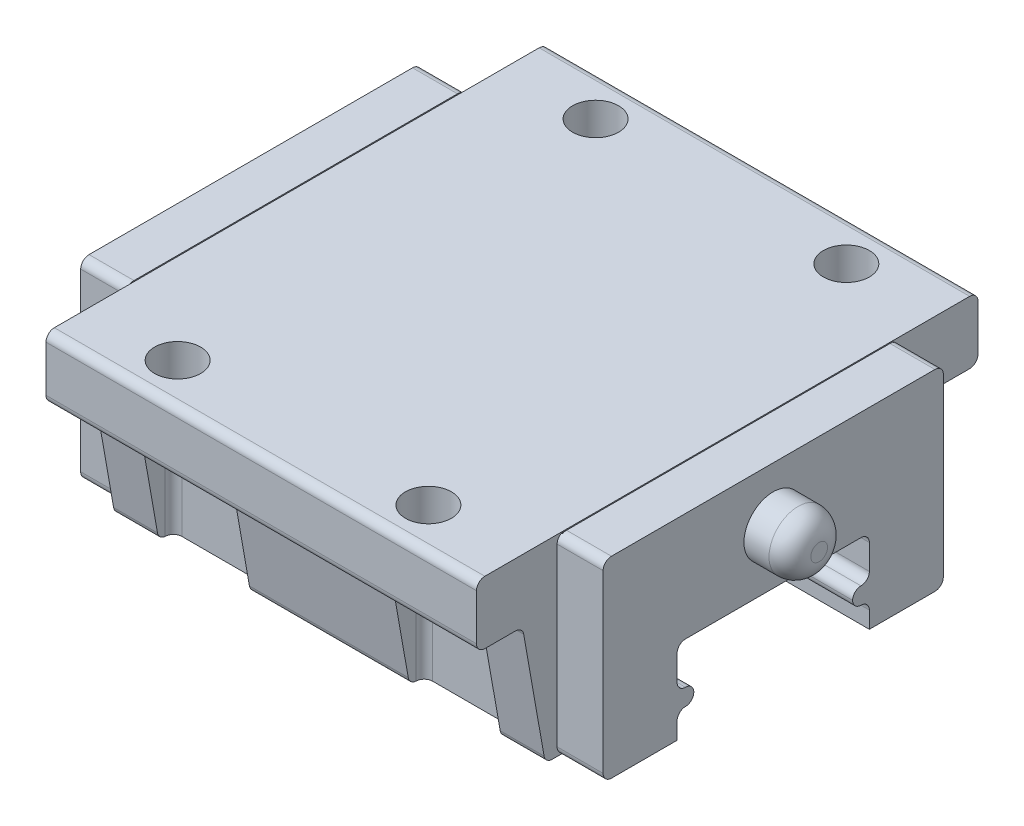
SolidWorks part; units mm, degrees
ref_plane "前视基准面" through (0, 0, 0) normal (0, 0, 1) x (1, 0, 0)
ref_plane "上视基准面" through (0, 0, 0) normal (0, 1, 0) x (1, 0, 0)
ref_plane "右视基准面" through (0, 0, 0) normal (1, 0, 0) x (0, 0, -1)
sketch "草图1" plane through (0, 0, 0) normal (1, 0, 0) x (0, 0, -1)
  line L0 (0, 35.1361) -> (0, -55.819) construction
  line L1 (-58, 0) -> (58, 0)
  line L2 (60, -2) -> (60, -13)
  line L3 (58, -15) -> (50.6782, -15)
  line L4 (48.7086, -16.6527) -> (43.8253, -44.3473)
  line L5 (41.8557, -46) -> (23, -46)
  line L6 (23, -46) -> (23, -42)
  line L7 (21, -40) -> (19, -40)
  line L8 (19, -40) -> (19, -36)
  line L9 (19, -36) -> (21, -36)
  line L10 (23, -34) -> (23, -28)
  line L11 (21, -26) -> (-21, -26)
  line L12 (-23, -34) -> (-23, -28)
  line L13 (-19, -36) -> (-21, -36)
  line L14 (-19, -40) -> (-19, -36)
  line L15 (-21, -40) -> (-19, -40)
  line L16 (-23, -46) -> (-23, -42)
  line L17 (-41.8557, -46) -> (-23, -46)
  line L18 (-48.7086, -16.6527) -> (-43.8253, -44.3473)
  line L19 (-58, -15) -> (-50.6782, -15)
  line L20 (-60, -2) -> (-60, -13)
  arc A0 (23, -34) -> (21, -36) centre (21, -34) cw
  arc A1 (23, -28) -> (21, -26) centre (21, -28) ccw
  arc A2 (21, -40) -> (23, -42) centre (21, -42) cw
  arc A3 (41.8557, -46) -> (43.8253, -44.3473) centre (41.8557, -44) ccw
  arc A4 (48.7086, -16.6527) -> (50.6782, -15) centre (50.6782, -17) cw
  arc A5 (58, -15) -> (60, -13) centre (58, -13) ccw
  arc A6 (60, -2) -> (58, 0) centre (58, -2) ccw
  arc A7 (-60, -2) -> (-58, 0) centre (-58, -2) cw
  arc A8 (-58, -15) -> (-60, -13) centre (-58, -13) cw
  arc A9 (-48.7086, -16.6527) -> (-50.6782, -15) centre (-50.6782, -17) ccw
  arc A10 (-41.8557, -46) -> (-43.8253, -44.3473) centre (-41.8557, -44) cw
  arc A11 (-21, -40) -> (-23, -42) centre (-21, -42) ccw
  arc A12 (-23, -28) -> (-21, -26) centre (-21, -28) cw
  arc A13 (-23, -34) -> (-21, -36) centre (-21, -34) ccw
  point P3 (-60, 0)
  point P25 (49, -15)
  point P28 (60, -15)
  point P31 (60, 0)
  point P53 (0, -26)
  point P56 (0, 0)
  point P57 (-60, -15)
  point P58 (-49, -15)
  dimension "D12" = 2
  dimension "D1" = 60
  dimension "D2" = 15
  dimension "D3" = 23
  dimension "D4" = 46
  dimension "D5" = 20
  dimension "D6" = 14
  dimension "D7" = 4
  dimension "D8" = 4
  dimension "D9" = 23
  dimension "D10" = 100
  dimension "D11" = 11
extrude "凸台-拉伸1" add sketch "草图1" along normal blind 125
fillet "圆角1" radius 2 4 edges at (62.5, -40, 19) (62.5, -36, 19) (62.5, -40, -19) (62.5, -36, -19)
sketch "草图2" plane through (0, 0, 0) normal (-1, 0, 0) x (0, 0, 1)
  line L0 (0, 0) -> (-40.7, 0)
  line L1 (-58, 0) -> (58, 0) construction
  line L2 (-40.7, 0) -> (-40.7, -46)
  line L4 (41.8557, -46) -> (23, -46) construction
  line L5 (40.7, -46) -> (40.7, 0)
  line L6 (40.7, 0) -> (0, 0)
  line L7 (-40.7, -46) -> (40.7, -46)
  dimension "D1" = 40.7
  dimension "D2" = 40.7
extrude "切除-拉伸1" cut sketch "草图2" against normal blind 11 flip side to cut
ref_plane "基准面1" through (62.5, 0, 0) normal (1, 0, 0) x (0, 0, -1)
mirror "镜向1" about plane through (62.5, 0, 0) normal (1, 0, 0) of "切除-拉伸1"
sketch "草图4" [suppressed] plane through (0, 0, 0) normal (-1, 0, 0) x (0, 0, 1)
  line L0 (-39.5478, -5) -> (-30.643, -5) construction
  line L1 (-35.7, 2.3404) -> (-35.7, -50.3028) construction
  line L2 (-39.5478, -41) -> (-29.0716, -41) construction
  line L3 (28.5478, -5) -> (43.2145, -5) construction
  line L4 (35.7, 2.3404) -> (35.7, -50.3028) construction
  line L5 (29.8573, -41) -> (39.4169, -41) construction
  line L6 (-40.7, 0) -> (-40.7, -46) construction
  line L7 (-40.7, 0) -> (40.7, 0) construction
  line L8 (-23, -46) -> (-40.7, -46) construction
  line L9 (40.7, -46) -> (40.7, 0) construction
  line L10 (40.7, -46) -> (23, -46) construction
  point P16 (-31.85, -46)
  dimension "D1" = 5
  dimension "D2" = 5
  dimension "D3" = 5
  dimension "D4" = 5
  dimension "D5" = 5
fillet "圆角2" radius 2 8 edges at (119.5, -46, 40.7) (119.5, -46, -40.7) (119.5, 0, -40.7) (119.5, 0, 40.7) (5.5, -46, -40.7) (5.5, -46, 40.7) (5.5, 0, 40.7) (5.5, 0, -40.7)
sketch "草图6" plane through (0, 0, 0) normal (0, 1, 0) x (1, 0, 0)
  line L0 (10.75, 40.7) -> (11, 40.7)
  line L1 (10.75, 40.7) -> (10.75, -40.7)
  line L2 (11, 40.7) -> (11, -40.7)
  line L3 (10.75, -40.7) -> (11, -40.7)
  line L4 (11, 38.7) -> (11, 58) construction
  dimension "D1" = 0.25
  dimension "D2" = 0.25
  dimension "D3" = 81.4
extrude "切除-拉伸2" cut sketch "草图6" against normal blind 0.25
sketch "草图7" plane through (0, 0, 0) normal (0, 1, 0) x (1, 0, 0)
  line L0 (-11.0108, 50) -> (123.8135, 50) construction
  line L1 (-23.1784, -50) -> (164.0449, -50) construction
  line L6 (114, -60) -> (11, -60) construction
  line L7 (32.5, 71.614) -> (32.5, -73.2191) construction
  line L8 (92.5, 71.614) -> (92.5, -73.2191) construction
  line L9 (62.5, -55.6343) -> (62.5, 55.6343) construction
  circle A0 centre (32.5, 50) radius 5.5
  circle A1 centre (92.5, 50) radius 5.5
  circle A2 centre (32.5, -50) radius 5.5
  circle A3 centre (92.5, -50) radius 5.5
  dimension "D5" = 11
  dimension "D6" = 11
  dimension "D7" = 11
  dimension "D8" = 11
  dimension "D1" = 100
  dimension "D2" = 10
  dimension "D3" = 60
  dimension "D4" = 30
extrude "切除-拉伸3" cut sketch "草图7" against normal blind 15
sketch "草图9" plane through (0, 0, 60) normal (0, 0, 1) x (1, 0, 0)
  line L0 (32.5, 13.1232) -> (32.5, -58.3058) construction
  line L1 (92.5, 12.3791) -> (92.5, -66.2423) construction
  line L2 (62.5, -41.63) -> (62.5, 41.63) construction
  line L3 (32.5, -15) -> (21.5, -15)
  line L4 (37.958, -15) -> (27.042, -15) construction
  line L5 (27.042, -15) -> (11, -15) construction
  line L6 (21.5, -15) -> (21.5, -44.3473)
  line L7 (114, -44.3473) -> (11, -44.3473) construction
  line L8 (21.5, -44.3473) -> (21.5, -46)
  line L9 (43.5, -44.3473) -> (43.5, -15)
  line L10 (87.042, -15) -> (37.958, -15) construction
  line L11 (43.5, -15) -> (32.5, -15)
  line L12 (92.5, -15) -> (81.5, -15)
  line L13 (97.958, -15) -> (87.042, -15) construction
  line L14 (81.5, -15) -> (81.5, -44.3473)
  line L15 (81.5, -44.3473) -> (81.5, -46)
  line L16 (103.5, -44.3473) -> (103.5, -15)
  line L17 (114, -15) -> (97.958, -15) construction
  line L18 (103.5, -15) -> (92.5, -15)
  line L19 (114, -46) -> (11, -46) construction
  line L20 (21.5, -46) -> (43.5, -46)
  line L21 (43.5, -46) -> (43.5, -44.3473)
  line L22 (81.5, -46) -> (103.5, -46)
  line L23 (103.5, -46) -> (103.5, -44.3473)
  dimension "D1" = 60
  dimension "D2" = 30
  dimension "D3" = 11
  dimension "D4" = 11
  dimension "D5" = 11
  dimension "D6" = 11
extrude "切除-拉伸4" cut sketch "草图9" against normal blind 20
fillet "圆角5" radius 2 4 edges at (43.5, -30.5, 40) (21.5, -30.5, 40) (103.5, -30.5, 40) (81.5, -30.5, 40)
mirror "镜向2" about plane through (0, 0, 0) normal (0, 0, 1) of "切除-拉伸4", "圆角5"
mirror "镜向3" about plane through (62.5, 0, 0) normal (1, 0, 0) of "切除-拉伸2"
sketch "草图10" plane through (125, 0, 0) normal (1, 0, 0) x (0, 0, -1)
  line L0 (0, 21.0667) -> (0, -78.4577) construction
  line L1 (-11.0001, -13) -> (9.5596, -13) construction
  line L2 (38.7, 0) -> (-38.7, 0) construction
  circle A0 centre (0, -13) radius 7
  point P7 (0, -13)
  dimension "D2" = 14
  dimension "D1" = 13
extrude "凸台-拉伸2" add sketch "草图10" along normal blind 11
fillet "圆角6" radius 5 1 edges at (136, -13, -7)
